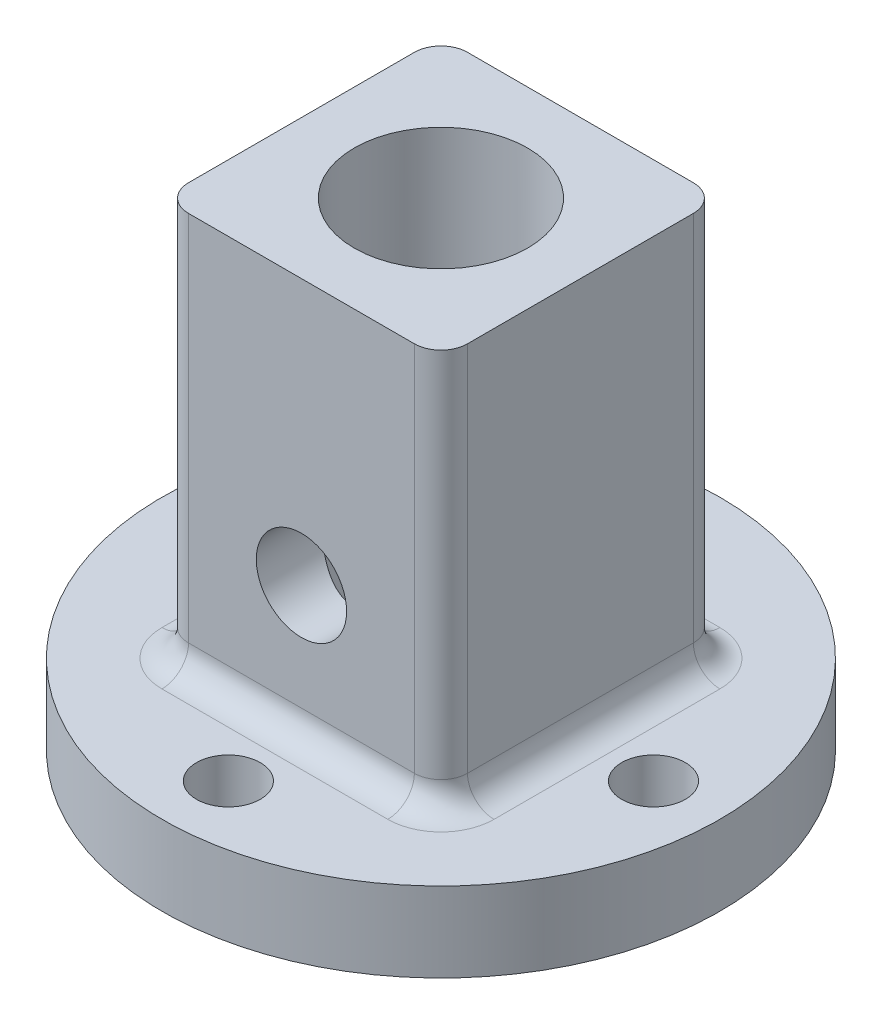
SolidWorks part; units mm, degrees
ref_plane "Front Plane" through (0, 0, 0) normal (0, 0, 1) x (1, 0, 0)
ref_plane "Top Plane" through (0, 0, 0) normal (0, 1, 0) x (1, 0, 0)
ref_plane "Right Plane" through (0, 0, 0) normal (1, 0, 0) x (0, 0, -1)
sketch "Sketch1" plane through (0, 0, 0) normal (0, 0, 1) x (1, 0, 0)
  line L3 (3.2639, 3) -> (10.5, 3)
  line L4 (10.5, 3) -> (10.5, 0)
  line L5 (10.5, 0) -> (3.2639, 0)
  line L6 (0, 0) -> (0, 10.6834) construction
  line L7 (3.2639, 0) -> (3.2639, 3)
  dimension "D1" = 3.2639
  dimension "D2" = 10.5
  dimension "D5" = 3
revolve "Revolve1" add sketch "Sketch1" angle 360 about L6
ref_axis "Axis1" through (0, 13.65, 0) along (0, -1, 0)
ref_plane "Plane1" through (0, 0, 0) normal (-0.7071, 0, 0.7071) x (0, -1, 0)
sketch "Sketch7" plane through (0, 3, 0) normal (0, 1, 0) x (1, 0, 0)
  line L1 (-5.25, 5.25) -> (5.25, 5.25)
  line L2 (-5.25, 5.25) -> (-5.25, -5.25)
  line L3 (-5.25, -5.25) -> (5.25, -5.25)
  line L4 (5.25, 5.25) -> (5.25, -5.25)
  line L5 (-5.25, 5.25) -> (5.25, -5.25) construction
  line L6 (-5.25, -5.25) -> (5.25, 5.25) construction
  circle A0 centre (0, 0) radius 3.2639 construction
  circle A1 centre (0, 0) radius 3.2639
  point P0 (0, 0)
  dimension "D1" = 10.5
extrude "Boss-Extrude1" add sketch "Sketch7" along normal blind 15
sketch "Sketch3" plane through (12.0711, 0, 5.25) normal (0, 0, -1) x (-1, 0, 0)
  line L2 (22.5711, 3) -> (1.5711, 3) construction
  circle A0 centre (12.0711, 8) radius 1.7
  dimension "D1" = 3.4
  dimension "D2" = 5
extrude "Cut-Extrude1" cut sketch "Sketch3" along normal through all contours A0
sketch "Sketch4" plane through (0, 3, 0) normal (0, 1, 0) x (1, 0, 0)
  line L0 (0, 0) -> (0, 8) construction
  line L1 (0, 0) -> (0, 8) construction
  line L2 (0, 0) -> (8, 0) construction
  line L3 (0, 9.2) -> (0, 10.5) construction
  circle A0 centre (0, 8) radius 1.2
  circle A1 centre (8, 0) radius 1.2
  circle A2 centre (0, -8) radius 1.2
  circle A3 centre (-8, 0) radius 1.2
  circle A4 centre (0, 8) radius 1.9 construction
  circle A6 centre (0, 0) radius 10.5 construction
  dimension "D2" = 2.4
  dimension "D6" = 3.8
  dimension "D1" = 8
  dimension "D4" = 90
  dimension "D5" = 8
  dimension "D7" = 1.3
  dimension "D3" = 4
extrude "Cut-Extrude2" cut sketch "Sketch4" against normal through all
fillet "Fillet1" radius 1 4 edges at (5.25, 10.5, -5.25) (-5.25, 10.5, -5.25) (5.25, 10.5, 5.25) (-5.25, 10.5, 5.25)
fillet "Fillet2" radius 1 8 edges at (-4.9571, 3, 4.9571) (-5.25, 3, 0) (-4.9571, 3, -4.9571) (0, 3, -5.25) (4.9571, 3, -4.9571) (5.25, 3, 0) (4.9571, 3, 4.9571) (0, 3, 5.25)
sketch "Sketch8" plane through (0, 0, 0) normal (0, -1, 0) x (1, 0, 0)
  circle A0 centre (0, 0) radius 4.25
  dimension "D1" = 8.5
extrude "Cut-Extrude3" cut sketch "Sketch8" against normal blind 3
fillet "Fillet3" radius 1 1 edges at (0, 3, -4.25)
